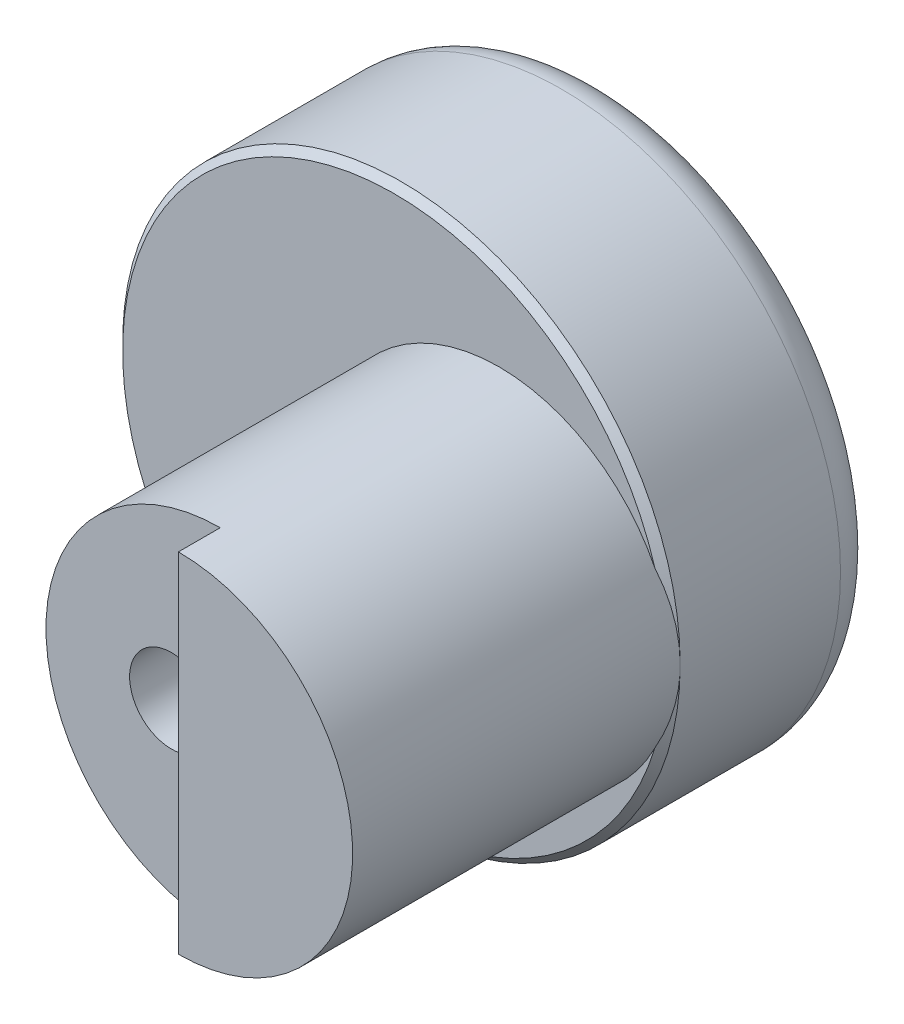
SolidWorks part; units mm, degrees
ref_plane "Front Plane" through (0, 0, 0) normal (0, 0, 1) x (1, 0, 0)
ref_plane "Top Plane" through (0, 0, 0) normal (0, 1, 0) x (1, 0, 0)
ref_plane "Right Plane" through (0, 0, 0) normal (1, 0, 0) x (0, 0, -1)
sketch "Sketch1" plane through (0, 0, 0) normal (0, 0, 1) x (1, 0, 0)
  circle A0 centre (0, 0) radius 20
  dimension "D1" = 40
extrude "Boss-Extrude1" add sketch "Sketch1" along normal blind 15
sketch "Sketch2" plane through (0, 0, 15) normal (0, 0, 1) x (1, 0, 0)
  circle A0 centre (7.5, 0) radius 12.5
  circle A1 centre (0, 0) radius 20 construction
  dimension "D1" = 25
extrude "Boss-Extrude2" add sketch "Sketch2" along normal blind 23
sketch "Sketch3" plane through (0, 0, 38) normal (0, 0, 1) x (1, 0, 0)
  circle A0 centre (4, 0) radius 3
  dimension "D1" = 6
  dimension "D2" = 4
extrude "Cut-Extrude1" cut sketch "Sketch3" against normal through all
fillet "Fillet1" radius 3 1 edges at (20, 0, 0)
chamfer "Chamfer1" distance 0.5 angle 45 1 edges at (20, 0, 15)
sketch "Sketch4" plane through (0, 0, 15) normal (0, 0, 1) x (1, 0, 0)
  line L0 (-34.4536, 0) -> (29.718, 0) construction
  line L1 (7.5, 20.8051) -> (7.5, -22.7101) construction
  point P6 (4, 0)
sketch "Sketch5" plane through (0, 0, 38) normal (0, 0, 1) x (1, 0, 0)
  line L0 (7.5, 12.5) -> (7.5, -12.5)
  line L1 (7.5, 20.8051) -> (7.5, -22.7101) construction
  arc A0 (18.6833, 5.5842) -> (18.6833, -5.5842) centre (7.5, 0) ccw construction
  arc A1 (7.5, 12.5) -> (7.5, -12.5) centre (4, 0) ccw
extrude "Cut-Extrude2" cut sketch "Sketch5" against normal blind 3
sketch "Sketch6" plane through (0, 0, 38) normal (0, 0, 1) x (1, 0, 0)
  line L0 (-7.6422, 0) -> (22.3103, 0) construction
  line L1 (4, 20.9236) -> (4, -24.868) construction
  point P6 (4, 0)
